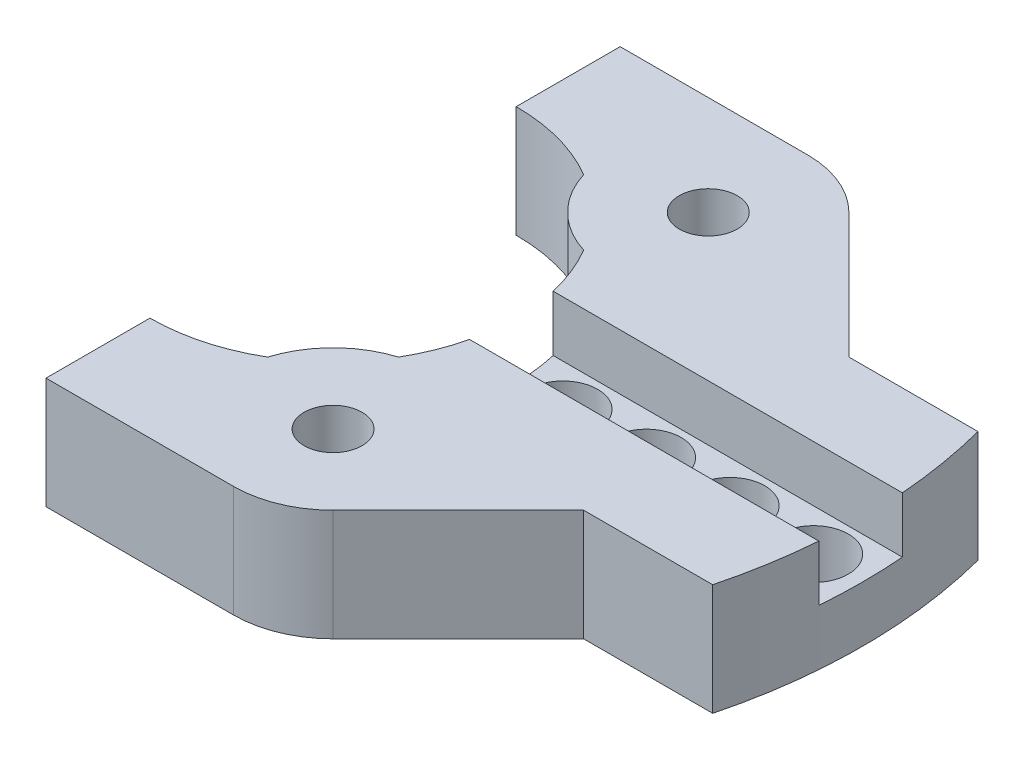
SolidWorks part; units mm, degrees
ref_plane "Front Plane" through (0, 0, 0) normal (0, 0, 1) x (1, 0, 0)
ref_plane "Top Plane" through (0, 0, 0) normal (0, 1, 0) x (1, 0, 0)
ref_plane "Right Plane" through (0, 0, 0) normal (1, 0, 0) x (0, 0, -1)
sketch "Sketch1" plane through (0, 0, 0) normal (0, 1, 0) x (1, 0, 0)
  line L0 (0, 13.4704) -> (0, -13.4704) construction
  line L8 (0, 20.6141) -> (0, 13.1512)
  line L9 (13.4704, 20.6141) -> (0, 20.6141)
  line L10 (27.5186, 9.525) -> (36.7869, 9.525)
  line L12 (18.5218, -18.5218) -> (27.5186, -9.525)
  line L14 (18.5218, 18.5218) -> (27.5186, 9.525)
  line L15 (27.5186, -9.525) -> (36.7869, -9.525)
  line L16 (13.4704, -20.6141) -> (0, -20.6141)
  line L17 (0, -20.6141) -> (0, -13.1512)
  arc A0 (6.6498, 11.3461) -> (0, 13.1512) centre (0, 0) ccw
  circle A1 centre (13.4704, 13.4704) radius 2.0828
  arc A2 (6.6498, 11.3461) -> (11.3461, 6.6498) centre (13.4704, 13.4704) ccw
  circle A3 centre (13.4704, 13.4704) radius 7.1438 construction
  arc A4 (11.3461, -6.6498) -> (11.3461, 6.6498) centre (0, 0) ccw
  arc A5 (13.4704, 20.6141) -> (18.5218, 18.5218) centre (13.4704, 13.4704) cw
  arc A6 (36.7869, -9.525) -> (36.7869, 9.525) centre (0, 0) ccw
  arc A7 (13.4704, -20.6141) -> (18.5218, -18.5218) centre (13.4704, -13.4704) ccw
  arc A8 (6.6498, -11.3461) -> (11.3461, -6.6498) centre (13.4704, -13.4704) cw
  circle A9 centre (13.4704, -13.4704) radius 2.0828
  arc A10 (6.6498, -11.3461) -> (0, -13.1512) centre (0, 0) cw
  circle A15 centre (16.5, 0) radius 2.5
  circle A16 centre (22.5, 0) radius 2.5
  circle A17 centre (28.5, 0) radius 2.5
  circle A18 centre (34.5, 0) radius 2.5
  point P20 (13.4704, 13.4704)
extrude "Boss-Extrude2" add sketch "Sketch1" along normal blind 4
sketch "Sketch5" plane through (0, 0, 0) normal (0, -1, 0) x (1, 0, 0)
  line L0 (16.5, 0) -> (34.5, 0)
  line L8 (36.7869, 9.525) -> (27.5186, 9.525)
  line L9 (27.5186, 9.525) -> (18.5218, 18.5218)
  line L10 (13.4704, 20.6141) -> (0, 20.6141)
  line L11 (0, 20.6141) -> (0, 13.1512)
  line L12 (0, -13.1512) -> (0, -20.6141)
  line L13 (0, -20.6141) -> (13.4704, -20.6141)
  line L14 (18.5218, -18.5218) -> (27.5186, -9.525)
  line L15 (27.5186, -9.525) -> (36.7869, -9.525)
  line L16 (36.7869, 9.525) -> (27.5186, 9.525)
  line L17 (27.5186, 9.525) -> (18.5218, 18.5218)
  line L18 (13.4704, 20.6141) -> (0, 20.6141)
  line L19 (0, 20.6141) -> (0, 13.1512)
  line L20 (0, -13.1512) -> (0, -20.6141)
  line L21 (0, -20.6141) -> (13.4704, -20.6141)
  line L22 (18.5218, -18.5218) -> (27.5186, -9.525)
  line L23 (27.5186, -9.525) -> (36.7869, -9.525)
  circle A0 centre (13.4704, -13.4704) radius 3.429
  circle A1 centre (13.4704, 13.4704) radius 3.429
  arc A2 (0, -13.1512) -> (0, 13.1512) centre (0, 0) ccw
  circle A3 centre (16.5, 0) radius 2.5
  circle A4 centre (22.5, 0) radius 2.5
  circle A5 centre (28.5, 0) radius 2.5
  circle A6 centre (34.5, 0) radius 2.5
  arc A8 (36.7869, -9.525) -> (36.7869, 9.525) centre (0, 0) ccw
  arc A9 (18.5218, 18.5218) -> (13.4704, 20.6141) centre (13.4704, 13.4704) ccw
  arc A10 (6.6498, 11.3461) -> (0, 13.1512) centre (0, 0) ccw
  arc A11 (6.6498, 11.3461) -> (11.3461, 6.6498) centre (13.4704, 13.4704) ccw
  arc A12 (11.3461, -6.6498) -> (11.3461, 6.6498) centre (0, 0) ccw
  arc A13 (11.3461, -6.6498) -> (6.6498, -11.3461) centre (13.4704, -13.4704) ccw
  arc A14 (0, -13.1512) -> (6.6498, -11.3461) centre (0, 0) ccw
  arc A15 (13.4704, -20.6141) -> (18.5218, -18.5218) centre (13.4704, -13.4704) ccw
  arc A16 (36.7869, -9.525) -> (36.7869, 9.525) centre (0, 0) ccw
  arc A17 (18.5218, 18.5218) -> (13.4704, 20.6141) centre (13.4704, 13.4704) ccw
  arc A23 (13.4704, -20.6141) -> (18.5218, -18.5218) centre (13.4704, -13.4704) ccw
  dimension "D2" = 4
  dimension "D1" = 0
extrude "Boss-Extrude3" add sketch "Sketch5" along normal blind 4
sketch "Sketch6" plane through (0, 4, 0) normal (0, 1, 0) x (1, 0, 0)
  line L1 (12.8045, -3) -> (37.8814, -3)
  line L9 (36.7869, 9.525) -> (27.5186, 9.525)
  line L10 (12.8045, 3) -> (37.8814, 3)
  line L11 (27.5186, 9.525) -> (18.5218, 18.5218)
  line L12 (13.4704, 20.6141) -> (0, 20.6141)
  line L13 (0, 20.6141) -> (0, 13.1512)
  line L14 (0, -13.1512) -> (0, -20.6141)
  line L15 (0, -20.6141) -> (13.4704, -20.6141)
  line L16 (18.5218, -18.5218) -> (27.5186, -9.525)
  line L17 (27.5186, -9.525) -> (36.7869, -9.525)
  arc A8 (36.7869, -9.525) -> (36.7869, 9.525) centre (0, 0) ccw
  arc A9 (18.5218, 18.5218) -> (13.4704, 20.6141) centre (13.4704, 13.4704) ccw
  arc A10 (6.6498, 11.3461) -> (0, 13.1512) centre (0, 0) ccw
  arc A11 (6.6498, 11.3461) -> (11.3461, 6.6498) centre (13.4704, 13.4704) ccw
  arc A12 (11.3461, -6.6498) -> (11.3461, 6.6498) centre (0, 0) ccw
  arc A13 (11.3461, -6.6498) -> (6.6498, -11.3461) centre (13.4704, -13.4704) ccw
  arc A14 (0, -13.1512) -> (6.6498, -11.3461) centre (0, 0) ccw
  arc A15 (13.4704, -20.6141) -> (18.5218, -18.5218) centre (13.4704, -13.4704) ccw
  arc A16 (37.8814, -3) -> (37.8814, 3) centre (0, 0) ccw
  arc A20 (12.8045, -3) -> (12.8045, 3) centre (0, 0) ccw
  point P10 (0, 0)
  point P11 (0, 0)
  dimension "D1" = 0
extrude "Cut-Extrude2" cut sketch "Sketch6" against normal blind 4
